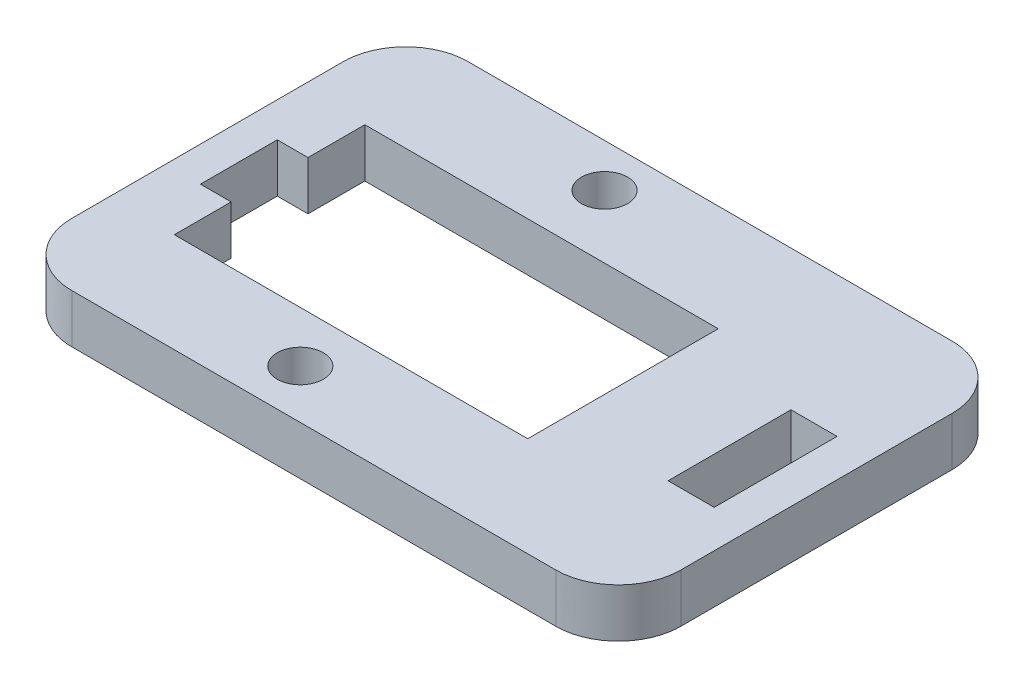
SolidWorks part; units mm, degrees
ref_plane "Front Plane" through (0, 0, 0) normal (0, 0, 1) x (1, 0, 0)
ref_plane "Top Plane" through (0, 0, 0) normal (0, 1, 0) x (1, 0, 0)
ref_plane "Right Plane" through (0, 0, 0) normal (1, 0, 0) x (0, 0, -1)
sketch "Sketch1" plane through (0, 0, 0) normal (0, 1, 0) x (1, 0, 0)
  line L0 (-15.5612, 5.9837) -> (7.4388, 5.9837)
  line L1 (7.4388, 5.9837) -> (7.4388, -6.4162)
  line L2 (7.4388, -6.4162) -> (-15.5612, -6.4162)
  line L3 (-15.5612, -6.4162) -> (-15.5612, -2.7163)
  line L4 (-15.5612, -2.7163) -> (-17.5613, -2.7163)
  line L5 (-17.5613, -2.7163) -> (-17.5613, 2.2836)
  line L6 (-17.5613, 2.2836) -> (-15.5612, 2.2836)
  line L7 (-15.5612, 2.2836) -> (-15.5612, 5.9837)
  line L8 (-15.7526, 12.8991) -> (15.7525, 12.8991)
  line L9 (19.82, 8.8318) -> (19.82, -8.8317)
  line L10 (15.7525, -12.8991) -> (-15.7526, -12.8991)
  line L11 (-19.82, -8.8317) -> (-19.82, 8.8318)
  line L12 (14.3743, 3.7836) -> (17.3744, 3.7836)
  line L13 (17.3744, 3.7836) -> (17.3744, -4.2164)
  line L14 (17.3744, -4.2164) -> (14.3743, -4.2164)
  line L15 (14.3743, -4.2164) -> (14.3743, 3.7836)
  line L16 (-5.5612, 10.0837) -> (-2.5613, 10.0836) construction
  line L17 (-4.0612, 11.5836) -> (-4.0613, 8.5837) construction
  line L18 (-4.0619, -8.2163) -> (-4.062, -11.2163) construction
  line L19 (-2.562, -9.7164) -> (-5.5619, -9.7162) construction
  circle A0 centre (-4.0612, 10.0836) radius 1.5
  circle A1 centre (-4.0619, -9.7163) radius 1.5
  spline S8 degree 3 poles (15.7525, 12.8991) (17.9896, 12.8991) (19.82, 11.0688) (19.82, 8.8318) knots 0.111111 0.111111 0.111111 0.111111 0.222222 0.222222 0.222222 0.222222
  spline S9 degree 3 poles (19.82, -8.8317) (19.82, -11.0689) (17.9896, -12.8991) (15.7525, -12.8991) knots 0.333333 0.333333 0.333333 0.333333 0.444444 0.444444 0.444444 0.444444
  spline S10 degree 3 poles (-15.7526, -12.8991) (-17.9897, -12.8991) (-19.82, -11.0689) (-19.82, -8.8317) knots 0.555556 0.555556 0.555556 0.555556 0.666667 0.666667 0.666667 0.666667
  spline S11 degree 3 poles (-19.82, 8.8318) (-19.82, 11.0688) (-17.9897, 12.8991) (-15.7526, 12.8991) knots 0.777778 0.777778 0.777778 0.777778 1 1 1 1
extrude "Boss-Extrude1" add sketch "Sketch1" along normal blind 3.175
